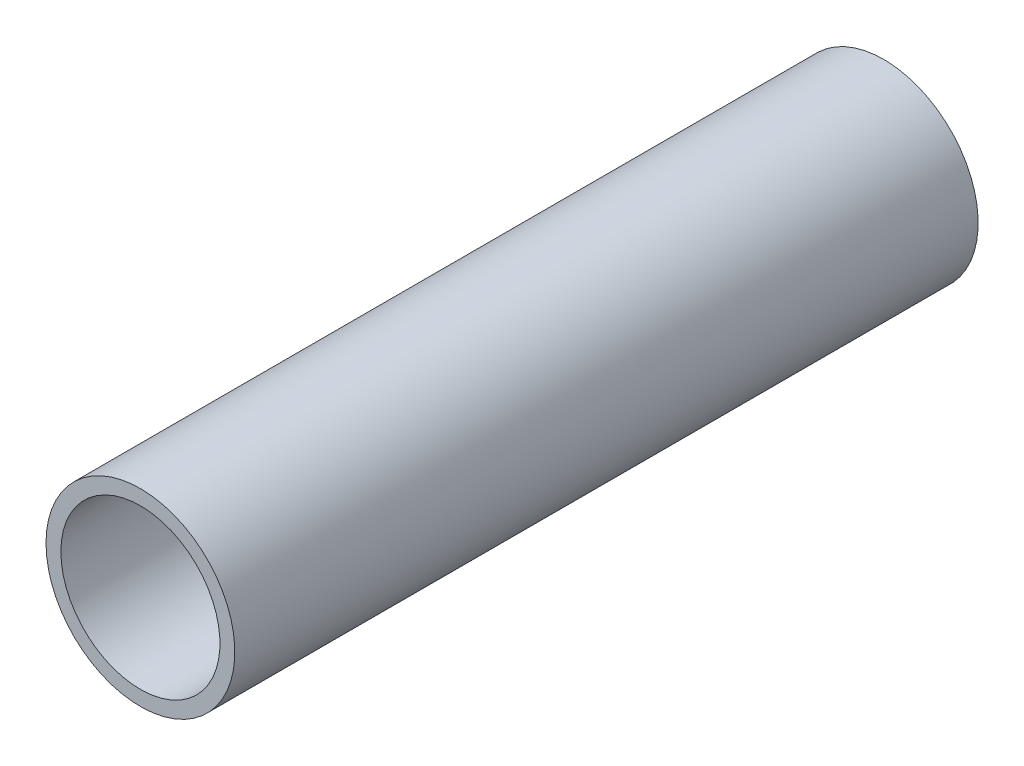
SolidWorks part; units mm, degrees
material "PVC Rigid"
ref_plane "Front Plane" through (0, 0, 0) normal (0, 0, 1) x (1, 0, 0)
ref_plane "Top Plane" through (0, 0, 0) normal (0, 1, 0) x (1, 0, 0)
ref_plane "Right Plane" through (0, 0, 0) normal (1, 0, 0) x (0, 0, -1)
sketch "Path" plane through (0, 0, 0) normal (1, 0, 0) x (0, 0, -1)
  line L0 (0, 0) -> (50, 0)
  dimension "Longitud" = 50
sweep "Sweep-Thin" add path "Path" circular profile diameter 1 parameters "D1"=1, "Diámetro"=12.7
